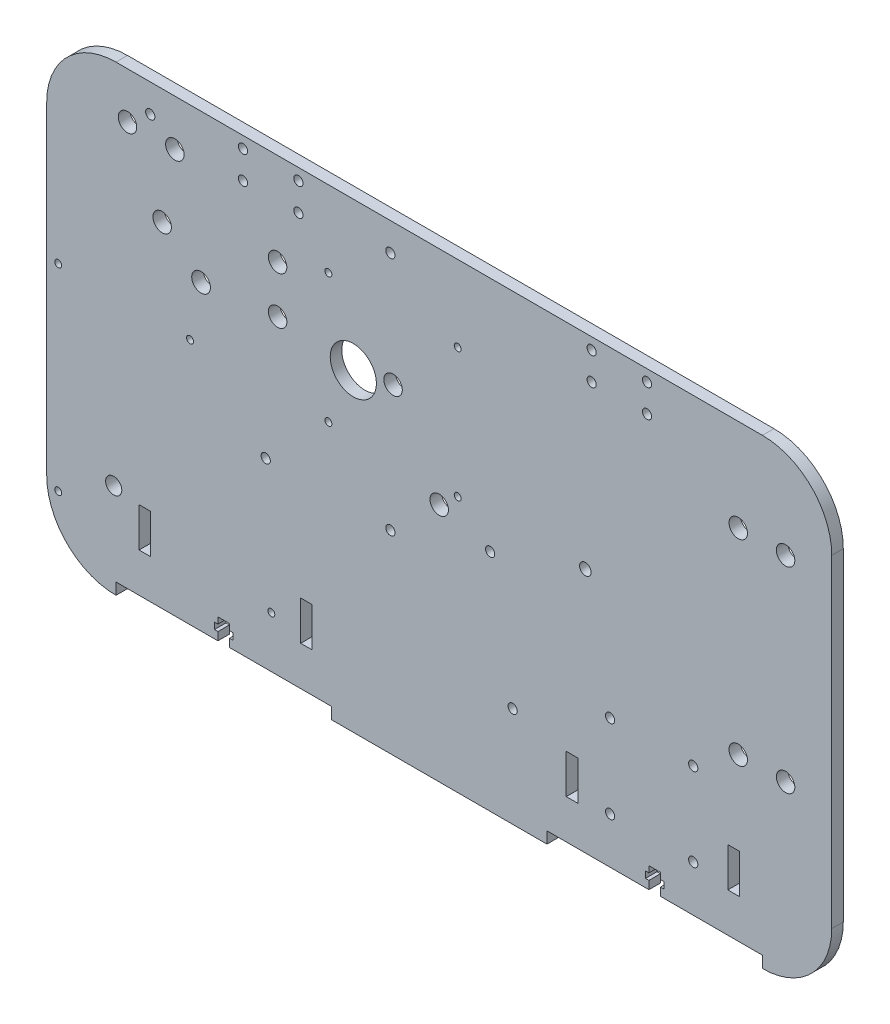
SolidWorks part; units mm, degrees
ref_plane "Alzado" through (0, 0, 0) normal (0, 0, 1) x (1, 0, 0)
ref_plane "Planta" through (0, 0, 0) normal (0, 1, 0) x (1, 0, 0)
ref_plane "Vista lateral" through (0, 0, 0) normal (1, 0, 0) x (0, 0, -1)
sketch "Croquis1" plane through (0, 0, 0) normal (0, 0, 1) x (1, 0, 0)
  line L1 (30, 0) -> (310, 0)
  line L2 (0, 30) -> (0, 170)
  line L3 (30, 200) -> (310, 200)
  line L4 (340, 30) -> (340, 170)
  arc A0 (30, 0) -> (0, 30) centre (30, 30) cw
  arc A1 (310, 0) -> (340, 30) centre (310, 30) ccw
  arc A2 (310, 200) -> (340, 170) centre (310, 170) cw
  arc A3 (0, 170) -> (30, 200) centre (30, 170) cw
  point P7 (0, 0)
  point P12 (340, 200)
  point P15 (0, 200)
  dimension "D3" = 30
  dimension "D1" = 200
  dimension "D2" = 340
extrude "Saliente-Extruir1" add sketch "Croquis1" along normal blind 5
sketch "Croquis2" plane through (0, 0, 5) normal (0, 0, -1) x (-1, 0, 0)
  line L0 (-55.5, 180) -> (-35, 180) construction
  line L2 (-310, 200) -> (-30, 200) construction
  line L3 (0, 170) -> (0, 30) construction
  line L4 (-100, 160) -> (-100, 139.5) construction
  line L5 (-310, 200) -> (-30, 200) construction
  line L6 (-299.5, 160) -> (-320, 160) construction
  line L7 (-340, 30) -> (-340, 170) construction
  line L8 (-320, 75) -> (-299.5, 75) construction
  line L9 (-30, 0) -> (-310, 0) construction
  line L10 (-100, 149.75) -> (-146.5265, 149.75) construction
  circle A0 centre (-55.5, 180) radius 4
  circle A1 centre (-35, 180) radius 4
  circle A2 centre (-100, 160) radius 4
  circle A3 centre (-100, 139.5) radius 4
  circle A4 centre (-299.5, 160) radius 4
  circle A5 centre (-320, 160) radius 4
  circle A6 centre (-320, 75) radius 4
  circle A7 centre (-299.5, 75) radius 4
  circle A8 centre (-150, 139) radius 4
  circle A9 centre (-170, 104) radius 4
  circle A10 centre (-50, 150) radius 4
  dimension "D1" = 8
  dimension "D10" = 40
  dimension "D14" = 8
  dimension "D19" = 8
  dimension "D2" = 20.5
  dimension "D3" = 35
  dimension "D4" = 20
  dimension "D5" = 20.5
  dimension "D6" = 40
  dimension "D7" = 100
  dimension "D8" = 20.5
  dimension "D9" = 20
  dimension "D11" = 20.5
  dimension "D12" = 20
  dimension "D13" = 75
  dimension "D15" = 150
  dimension "D16" = 61
  dimension "D17" = 35
  dimension "D18" = 20
  dimension "D20" = 50
  dimension "D21" = 50
extrude "Cortar-Extruir4" cut sketch "Croquis2" along normal blind 10
sketch "Croquis3" plane through (0, 0, 0) normal (0, 0, -1) x (-1, 0, 0)
  line L0 (-44.85, 187.84) -> (-148.85, 187.84) construction
  line L1 (-148.85, 187.84) -> (-148.85, 83.84) construction
  line L2 (-148.85, 83.84) -> (-94.85, 83.84) construction
  line L3 (-94.85, 83.84) -> (-44.85, 187.84) construction
  line L4 (-310, 200) -> (-30, 200) construction
  line L5 (0, 170) -> (0, 30) construction
  circle A0 centre (-148.85, 83.84) radius 2
  circle A1 centre (-94.85, 83.84) radius 2
  circle A2 centre (-44.85, 187.84) radius 2
  circle A3 centre (-148.85, 187.84) radius 2
  circle A4 centre (-132.79, 135.84) radius 10
  circle A5 centre (-66.85, 135.84) radius 4.05
  dimension "D1" = 4
  dimension "D5" = 20
  dimension "D6" = 8.1
  dimension "D2" = 104
  dimension "D3" = 104
  dimension "D4" = 54
  dimension "D7" = 16.06
  dimension "D8" = 52
  dimension "D9" = 52
  dimension "D10" = 82
  dimension "D11" = 12.16
  dimension "D12" = 66.85
extrude "Cortar-Extruir5" cut sketch "Croquis3" against normal blind 10
sketch "Croquis5" plane through (0, 0, 0) normal (0, 0, -1) x (-1, 0, 0)
  line L0 (-178, 167) -> (-122, 167) construction
  line L1 (-122, 167) -> (-122, 111) construction
  line L2 (-178, 167) -> (-178, 111) construction
  line L3 (-178, 111) -> (-122, 111) construction
  line L4 (-310, 200) -> (-30, 200) construction
  line L7 (0, 170) -> (0, 30) construction
  circle A0 centre (-178, 167) radius 1.5
  circle A1 centre (-122, 111) radius 1.5
  circle A2 centre (-122, 167) radius 1.5
  circle A3 centre (-178, 111) radius 1.5
  dimension "D1" = 3
  dimension "D4" = 3
  dimension "D2" = 56
  dimension "D3" = 56
  dimension "D5" = 33
  dimension "D6" = 122
extrude "Cortar-Extruir6" cut sketch "Croquis5" against normal blind 10
sketch "Croquis6" plane through (0, 0, 5) normal (0, 0, 1) x (1, 0, 0)
  line L0 (244, 61) -> (280, 61) construction
  line L1 (244, 61) -> (244, 25) construction
  line L2 (244, 25) -> (280, 25) construction
  line L3 (280, 25) -> (280, 61) construction
  line L4 (340, 30) -> (340, 170) construction
  line L5 (30, 0) -> (310, 0) construction
  circle A0 centre (244, 61) radius 2
  circle A1 centre (280, 61) radius 2
  circle A2 centre (244, 25) radius 2
  circle A3 centre (280, 25) radius 2
  dimension "D1" = 4
  dimension "D2" = 36
  dimension "D3" = 36
  dimension "D4" = 60
  dimension "D5" = 25
extrude "Cortar-Extruir7" cut sketch "Croquis6" against normal blind 10
sketch "Croquis7" plane through (0, 0, 5) normal (0, 0, 1) x (1, 0, 0)
  line L4 (30, 0) -> (310, 0)
  line L5 (340, 30) -> (340, 170)
  line L6 (310, 200) -> (30, 200)
  line L7 (0, 170) -> (0, 30)
  line L8 (30, 0) -> (310, 0)
  line L9 (340, 30) -> (340, 170)
  line L10 (310, 200) -> (30, 200)
  line L11 (0, 170) -> (0, 30)
  circle A0 centre (50, 150) radius 4 construction
  circle A1 centre (100, 160) radius 4 construction
  circle A2 centre (100, 139.5) radius 4 construction
  circle A3 centre (299.5, 75) radius 4 construction
  arc A4 (0, 30) -> (30, 0) centre (30, 30) ccw
  arc A5 (310, 0) -> (340, 30) centre (310, 30) ccw
  arc A6 (340, 170) -> (310, 200) centre (310, 170) ccw
  arc A7 (30, 200) -> (0, 170) centre (30, 170) ccw
  arc A8 (0, 30) -> (30, 0) centre (30, 30) ccw
  arc A9 (310, 0) -> (340, 30) centre (310, 30) ccw
  arc A10 (340, 170) -> (310, 200) centre (310, 170) ccw
  arc A11 (30, 200) -> (0, 170) centre (30, 170) ccw
  circle A12 centre (320, 75) radius 4 construction
  circle A13 centre (299.5, 160) radius 4 construction
  circle A14 centre (320, 160) radius 4 construction
  circle A15 centre (55.5, 180) radius 4 construction
  circle A16 centre (35, 180) radius 4 construction
  circle A17 centre (50, 150) radius 4
  circle A18 centre (100, 160) radius 4
  circle A19 centre (100, 139.5) radius 4
  circle A20 centre (299.5, 75) radius 4
  circle A21 centre (320, 75) radius 4
  circle A22 centre (299.5, 160) radius 4
  circle A23 centre (320, 160) radius 4
  circle A24 centre (55.5, 180) radius 4
  circle A25 centre (35, 180) radius 4
  dimension "D1" = 0
sketch "Croquis8" plane through (0, 0, 5) normal (0, 0, 1) x (1, 0, 0)
  line L0 (236, 195) -> (236, 183) construction
  line L1 (236, 195) -> (260, 195) construction
  line L2 (236, 183) -> (260, 183) construction
  line L3 (260, 183) -> (260, 195) construction
  line L4 (85, 195) -> (85, 183) construction
  line L5 (85, 195) -> (109, 195) construction
  line L6 (85, 183) -> (109, 183) construction
  line L7 (109, 183) -> (109, 195) construction
  line L8 (310, 200) -> (30, 200) construction
  line L9 (340, 30) -> (340, 170) construction
  line L10 (0, 170) -> (0, 30) construction
  circle A0 centre (236, 195) radius 2
  circle A1 centre (236, 183) radius 2
  circle A2 centre (260, 183) radius 2
  circle A3 centre (260, 195) radius 2
  circle A4 centre (85, 195) radius 2
  circle A5 centre (85, 183) radius 2
  circle A6 centre (109, 183) radius 2
  circle A7 centre (109, 195) radius 2
  dimension "D1" = 24
  dimension "D2" = 12
  dimension "D3" = 24
  dimension "D4" = 12
  dimension "D5" = 5
  dimension "D6" = 80
  dimension "D7" = 85
extrude "Cortar-Extruir8" cut sketch "Croquis8" against normal blind 10
sketch "Croquis9" plane through (0, 0, 0) normal (0, 0, -1) x (-1, 0, 0)
  line L0 (-233.2967, 111.4949) -> (-201.8, 43.4) construction
  line L1 (-201.8, 43.4) -> (-192.05, 97.4132) construction
  line L2 (-192.05, 97.4132) -> (-233.2967, 111.4949) construction
  line L3 (-62.0804, 111.91) -> (-4.98, 111.91) construction
  line L4 (-4.98, 111.91) -> (-4.98, 26.56) construction
  line L5 (-4.98, 26.56) -> (-97.2809, 27.16) construction
  line L6 (-62.0804, 111.91) -> (-97.2809, 27.16) construction
  line L8 (-30, 0) -> (-310, 0) construction
  line L9 (0, 170) -> (0, 30) construction
  line L10 (-340, 30) -> (-340, 170) construction
  circle A0 centre (-29.01, 40.6565) radius 3.5
  circle A1 centre (-62.0804, 111.91) radius 1.5
  circle A2 centre (-4.98, 111.91) radius 1.5
  circle A3 centre (-97.2809, 27.16) radius 1.5
  circle A4 centre (-4.98, 26.56) radius 1.5
  circle A5 centre (-233.2967, 111.4949) radius 2.5
  circle A6 centre (-201.8, 43.4) radius 2
  circle A7 centre (-192.05, 97.4132) radius 2
  dimension "D1" = 24.03
  dimension "D2" = 13.94
  dimension "D3" = 26.56
  dimension "D4" = 4.98
  dimension "D5" = 54.8862
  dimension "D6" = 43.5843
  dimension "D7" = 75.0264
  dimension "D8" = 43.4
  dimension "D9" = 138.2
extrude "Cortar-Extruir9" cut sketch "Croquis9" against normal blind 10
sketch "Croquis10" plane through (0, 0, 5) normal (0, 0, 1) x (1, 0, 0)
  line L0 (123.3333, 5) -> (123.3333, 0)
  line L1 (30, 0) -> (310, 0)
  line L2 (30, 0) -> (30, 5)
  line L3 (30, 5) -> (310, 5)
  line L4 (310, 0) -> (310, 5)
  line L5 (216.6667, 5) -> (216.6667, 0)
  point P10 (30, 2.5)
  line M48 (30, 0) -> (310, 0)
  dimension "D1" = 93.3333
  dimension "D2" = 93.3333
  dimension "D3" = 5
extrude "Cortar-Extruir10" cut sketch "Croquis10" against normal blind 10 contours L3 L2 L0 M48 | L3 L5 L1 L4 region at (76.6667, 2.5, 5) region at (263.3333, 2.5, 5)
sketch "Croquis12" plane through (0, 0, 5) normal (0, 0, 1) x (1, 0, 0)
  line L0 (76.6667, 5) -> (76.6667, 14) construction
  line L1 (30, 5) -> (123.3333, 5) construction
  line L2 (170, 0) -> (170, 18.6393) construction
  line L3 (123.3333, 0) -> (216.6667, 0) construction
  line L4 (74.1667, 5) -> (74.1667, 8.5)
  line L5 (74.1667, 8.5) -> (72.6667, 8.5)
  line L6 (72.6667, 8.5) -> (72.6667, 11.3)
  line L7 (72.6667, 11.3) -> (74.1667, 11.3)
  line L8 (74.1667, 11.3) -> (74.1667, 14)
  line L9 (74.1667, 14) -> (79.1667, 14)
  line L10 (79.1667, 8.5) -> (80.6667, 8.5)
  line L11 (79.1667, 5) -> (79.1667, 8.5)
  line L12 (80.6667, 8.5) -> (80.6667, 11.3)
  line L13 (80.6667, 11.3) -> (79.1667, 11.3)
  line L14 (79.1667, 11.3) -> (79.1667, 14)
  line L15 (263.3333, 5) -> (263.3333, 14) construction
  line L16 (260.8333, 11.3) -> (260.8333, 14)
  line L17 (259.3333, 11.3) -> (260.8333, 11.3)
  line L18 (259.3333, 8.5) -> (259.3333, 11.3)
  line L19 (260.8333, 5) -> (260.8333, 8.5)
  line L20 (260.8333, 8.5) -> (259.3333, 8.5)
  line L21 (265.8333, 14) -> (260.8333, 14)
  line L22 (265.8333, 11.3) -> (265.8333, 14)
  line L23 (267.3333, 11.3) -> (265.8333, 11.3)
  line L24 (267.3333, 8.5) -> (267.3333, 11.3)
  line L25 (265.8333, 8.5) -> (267.3333, 8.5)
  line L26 (265.8333, 5) -> (265.8333, 8.5)
  line L27 (74.1667, 5) -> (79.1667, 5)
  line L28 (260.8333, 5) -> (265.8333, 5)
  point P1 (76.6667, 14)
  dimension "D1" = 2.8
  dimension "D2" = 4
  dimension "D3" = 9
  dimension "D4" = 3.5
  dimension "D5" = 2.5
extrude "Cortar-Extruir14" cut sketch "Croquis12" against normal blind 5
sketch "Croquis13" plane through (0, 0, 5) normal (0, 0, 1) x (1, 0, 0)
  line L0 (170, 0) -> (170, 28.0268) construction
  line L1 (123.3333, 0) -> (216.6667, 0) construction
  line L2 (79.1667, 5) -> (123.3333, 5) construction
  line L3 (110, 5) -> (115, 5)
  line L4 (110, 5) -> (110, 39)
  line L5 (110, 39) -> (115, 39)
  line L6 (115, 5) -> (115, 39)
  line L7 (225, 5) -> (225, 39)
  line L8 (230, 39) -> (225, 39)
  line L9 (230, 5) -> (230, 39)
  line L10 (230, 5) -> (225, 5)
  line L11 (110, 22) -> (115, 22)
  line L12 (225, 22) -> (230, 22)
  line L13 (30, 5) -> (74.1667, 5) construction
  line L14 (40, 5) -> (45, 5)
  line L15 (40, 5) -> (40, 39)
  line L16 (40, 39) -> (45, 39)
  line L17 (45, 5) -> (45, 39)
  line L18 (40, 22) -> (45, 22)
  line L19 (300, 22) -> (295, 22)
  line L20 (295, 5) -> (295, 39)
  line L21 (300, 39) -> (295, 39)
  line L22 (300, 5) -> (300, 39)
  line L23 (300, 5) -> (295, 5)
  dimension "D1" = 5
  dimension "D2" = 60
  dimension "D3" = 34
  dimension "D4" = 5
  dimension "D5" = 70
extrude "Cortar-Extruir15" cut sketch "Croquis13" against normal blind 5 contours L15 L18 L17 L16 | L4 L11 L6 L5 | L7 L12 L9 L8 | L19 L22 L21 L20 region at (112.5, 30.5, 5) region at (227.5, 30.5, 5) region at (42.5, 30.5, 5) region at (297.5, 30.5, 5)
